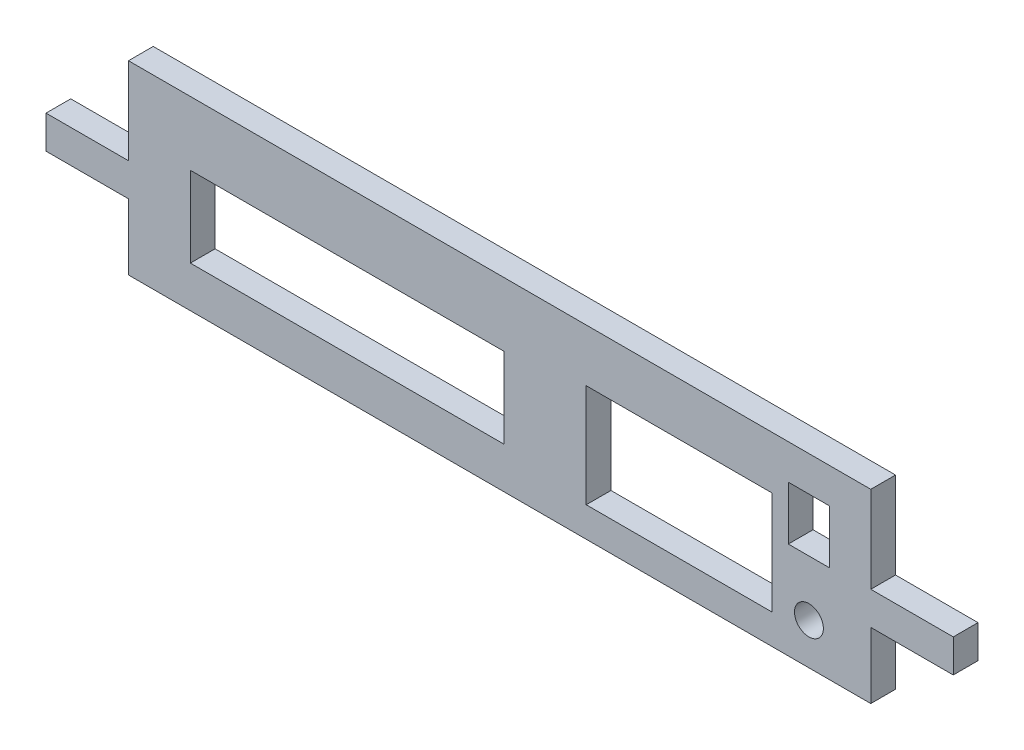
SolidWorks part; units mm, degrees
ref_plane "Plano frontal" through (0, 0, 0) normal (0, 0, 1) x (1, 0, 0)
ref_plane "Plano superior" through (0, 0, 0) normal (0, 1, 0) x (1, 0, 0)
ref_plane "Plano direito" through (0, 0, 0) normal (1, 0, 0) x (0, 0, -1)
sketch "Esboço1" plane through (0, 0, 0) normal (0, 0, 1) x (1, 0, 0)
  line L0 (-90, -6.5) -> (-90, -22.5)
  line L1 (-90, -6.5) -> (-110, -6.5)
  line L2 (-90, 22.5) -> (-90, 1.5)
  line L3 (-90, -22.5) -> (90, -22.5)
  line L4 (90, 22.5) -> (90, 1.5)
  line L5 (90, 1.5) -> (110, 1.5)
  line L6 (-90, -22.5) -> (90, 22.5) construction
  line L7 (-90, 1.5) -> (-110, 1.5)
  line L8 (-110, -6.5) -> (-110, 1.5)
  line L9 (90, -6.5) -> (110, -6.5)
  line L10 (110, -6.5) -> (110, 1.5)
  line L11 (90, -6.5) -> (90, -22.5)
  line L12 (0, 0) -> (0, 44.2972) construction
  line L20 (-90, 22.5) -> (90, 22.5)
  line L47 (-90, 22.5) -> (90, -22.5) construction
  line L48 (-75, -12.5) -> (1, -12.5)
  line L49 (-75, -12.5) -> (-75, 7)
  line L50 (-75, 7) -> (1, 7)
  line L51 (1, -12.5) -> (1, 7)
  line L52 (-75, -12.5) -> (1, 7) construction
  line L53 (-75, 7) -> (1, -12.5) construction
  line L54 (21, 9.75) -> (66, 9.75)
  line L55 (21, 9.75) -> (21, -15.25)
  line L56 (21, -15.25) -> (66, -15.25)
  line L57 (66, 9.75) -> (66, -15.25)
  line L58 (21, 9.75) -> (66, -15.25) construction
  line L59 (21, -15.25) -> (66, 9.75) construction
  line L60 (70, 14) -> (80, 14)
  line L61 (70, 14) -> (70, 1)
  line L62 (70, 1) -> (80, 1)
  line L63 (80, 14) -> (80, 1)
  line L64 (70, 14) -> (80, 1) construction
  line L65 (70, 1) -> (80, 14) construction
  circle A0 centre (75, -12.5) radius 3.5
  point P0 (0, 0)
  point P16 (0, 0)
  point P25 (75, 7.5)
  point P37 (43.5, -2.75)
  point P54 (-37, -2.75)
  dimension "D22" = 7
  dimension "D3" = 180
  dimension "D4" = 45
  dimension "D5" = 20
  dimension "D6" = 8
  dimension "D7" = 16
  dimension "D13" = 19.5
  dimension "D14" = 76
  dimension "D15" = 15
  dimension "D16" = 10
  dimension "D17" = 45
  dimension "D18" = 25
  dimension "D19" = 20
  dimension "D20" = 13
  dimension "D21" = 10
  dimension "D23" = 10
  dimension "D24" = 10
  dimension "D25" = 20
extrude "Ressalto-extrusão1" add sketch "Esboço1" along normal blind 6
